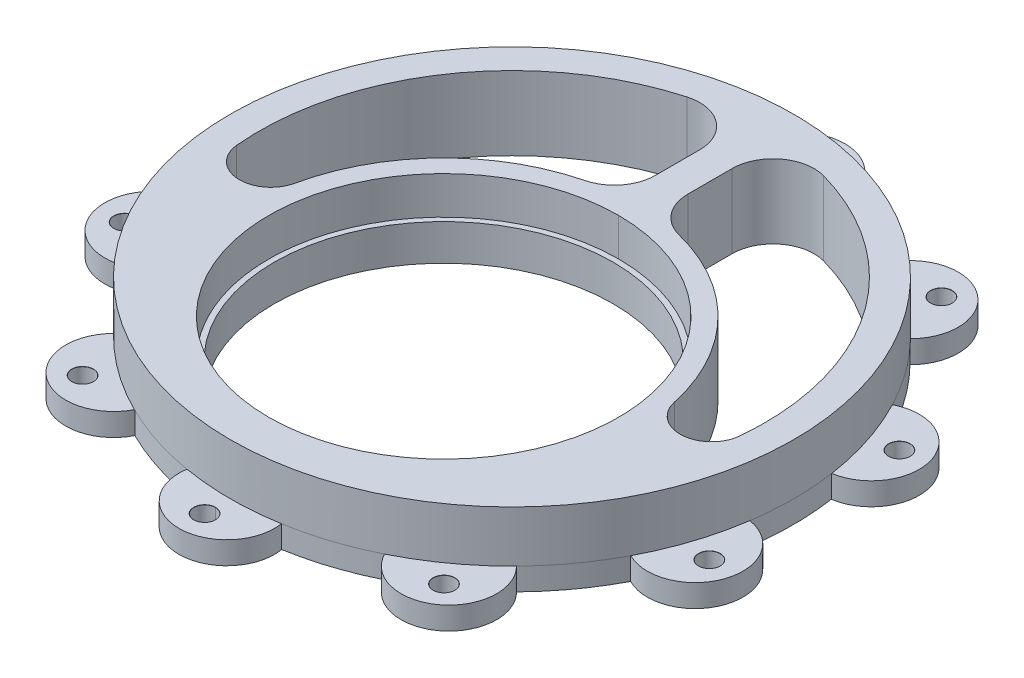
SolidWorks part; units mm, degrees
material "6061-T6 (SS)"
ref_plane "X-Y Datum" through (0, 0, 0) normal (0, 0, 1) x (1, 0, 0)
ref_plane "X-Z Datum" through (0, 0, 0) normal (0, 1, 0) x (1, 0, 0)
ref_plane "Y-Z Datum" through (0, 0, 0) normal (1, 0, 0) x (0, 0, -1)
sketch "Sketch1" plane through (0, 0, 0) normal (0, 1, 0) x (1, 0, 0)
  line L0 (0, 0) -> (0, -12.7) construction
  line L1 (0, -43.0151) -> (0, 43.0151) construction
  line L2 (0, 52.3875) -> (0, 61.9125) construction
  circle A0 centre (0, -12.7) radius 30.988
  circle A1 centre (0, 0) radius 52.3875 construction
  circle A2 centre (0, 0) radius 61.9125
  circle A3 centre (0, 0) radius 57.15 construction
  point P12 (0, 57.15)
  dimension "D2" = 61.976
  dimension "D3" = 104.775
  dimension "D4" = 123.825
  dimension "D5" = 114.3
  dimension "D1" = 12.7
extrude "Slotted-Body Extrude" add sketch "Sketch1" along normal blind 4.191
sketch "Sketch5" plane through (0, 4.191, 0) normal (0, 1, 0) x (1, 0, 0)
  circle A0 centre (0, 0) radius 52.3875 construction
  circle A1 centre (0, 0) radius 52.3875
extrude "Boss-Extrude3" add sketch "Sketch5" along normal blind 9.525
sketch "Sketch6" plane through (0, 0, 0) normal (0, -1, 0) x (1, 0, 0)
  line L0 (0, -79.2756) -> (0, 0) construction
  line L2 (3.014, -37.9067) -> (3.014, -29.6741)
  line L4 (-3.014, -37.9067) -> (-3.014, -29.6741)
  circle A0 centre (0, 12.7) radius 30.988 construction
  circle A1 centre (0, 12.7) radius 30.988 construction
  circle A2 centre (0, 12.7) radius 32.512
  arc A9 (-35.2562, 5.0907) -> (-8.7792, -22.2832) centre (0, 12.7) ccw
  arc A10 (-46.783, 4.406) -> (-12.6921, -45.2435) centre (0, 0) ccw
  arc A11 (-46.783, 4.406) -> (-35.2562, 5.0907) centre (-40.9667, 3.8583) cw
  arc A19 (-3.014, -29.6741) -> (-8.7792, -22.2832) centre (-10.634, -29.6741) ccw
  arc A20 (-3.014, -37.9067) -> (-12.6921, -45.2435) centre (-10.634, -37.9067) cw
  circle A21 centre (0, 0) radius 61.9125 construction
  arc A27 (46.783, 4.406) -> (35.2562, 5.0907) centre (40.9667, 3.8583) ccw
  arc A28 (46.783, 4.406) -> (12.6921, -45.2435) centre (0, 0) cw
  arc A29 (3.014, -37.9067) -> (12.6921, -45.2435) centre (10.634, -37.9067) ccw
  arc A30 (3.014, -29.6741) -> (8.7792, -22.2832) centre (10.634, -29.6741) cw
  arc A31 (35.2562, 5.0907) -> (8.7792, -22.2832) centre (0, 12.7) cw
  point P30 (0, 0)
  point P31 (-3.014, -23.2419)
  point P32 (0, 0)
  point P36 (-3.014, -46.8932)
  dimension "D1" = 65.024
  dimension "D2" = 7.62
  dimension "D3" = 5.842
  dimension "D4" = 46.99
  dimension "D5" = 7.62
  dimension "D6" = 36.068
  dimension "D8" = 8.2326
extrude "Cut-Extrude5" cut sketch "Sketch6" against normal through all
sketch "Sketch8" plane through (0, 0, 0) normal (0, -1, 0) x (1, 0, 0)
  circle A0 centre (0, 12.7) radius 32.512 construction
  circle A1 centre (0, 12.7) radius 32.512
  circle A2 centre (0, 12.7) radius 31.496
  dimension "D1" = 62.992
extrude "Boss-Extrude4" add sketch "Sketch8" against normal blind 6.7 separate body
hole_wizard "Ø4.0mm Dowel Hole2" positions "Sketch9" profile "Sketch10" hole size "Ø4.0" standard "ANSI Metric" end condition through all
sketch "Sketch9" plane through (0, 4.191, 0) normal (0, 1, 0) x (1, 0, 0)
  point P0 (0, 57.15)
sketch "Sketch10" plane through (0, 4.191, -57.15) normal (1, 0, 0) x (0, 0, 1)
  line L0 (0, 0) -> (0, 4.191)
  line L1 (0, 4.191) -> (2, 4.191)
  line L2 (2, 4.191) -> (2, 0.025)
  line L3 (2, 0.025) -> (2.025, 0)
  line L5 (2.025, 0) -> (0, 0)
  line L6 (-2, 0.025) -> (-2.025, 0) construction
  line L11 (0, -6.35) -> (0, 107.95) construction
  dimension "Thru Hole Dia." = 4
  dimension "Thru Hole Depth" = 4.191
  dimension "Near C'Sink Dia." = 4.05
  dimension "Near C'Sink Angle" = 90
pattern_circular "CirPattern1" count 10 over 360 about axis through (0, 13.716, 0) along (0, -1, 0) of "Ø4.0mm Dowel Hole2"
ref_point "Point1"
ref_plane "Plane1" through (0, 0, 0) normal (1, 0, 0) x (0, 0, -1)
split line "Split Line1"
ref_point "Point4"
ref_point "Point5"
split line "Split Line2"
split line "Split Line3"
sketch "Sketch14" plane through (0, 4.191, 0) normal (0, 1, 0) x (1, 0, 0)
  arc A2 (-8.7727, 51.5833) -> (8.7727, 51.5833) centre (0, 53.0225) cw
  circle A3 centre (0, 0) radius 61.9125 construction
  circle A4 centre (0, 0) radius 52.324 construction
  arc A5 (-8.7727, 51.5833) -> (8.7727, 51.5833) centre (0, 0) cw
  arc A6 (23.2226, 46.8883) -> (37.4172, 36.5753) centre (0, 0) cw
  arc A7 (23.2226, 46.8883) -> (37.4172, 36.5753) centre (31.1658, 42.8961) cw
  arc A8 (46.3477, 24.2835) -> (51.7696, 7.5968) centre (0, 0) cw
  arc A9 (46.3477, 24.2835) -> (51.7696, 7.5968) centre (50.4274, 16.3849) cw
  arc A10 (51.7696, -7.5968) -> (46.3477, -24.2835) centre (0, 0) cw
  arc A11 (51.7696, -7.5968) -> (46.3477, -24.2835) centre (50.4274, -16.3849) cw
  arc A12 (37.4172, -36.5753) -> (23.2226, -46.8883) centre (0, 0) cw
  arc A13 (37.4172, -36.5753) -> (23.2226, -46.8883) centre (31.1658, -42.8961) cw
  arc A14 (8.7727, -51.5833) -> (-8.7727, -51.5833) centre (0, 0) cw
  arc A15 (8.7727, -51.5833) -> (-8.7727, -51.5833) centre (0, -53.0225) cw
  arc A16 (-23.2226, -46.8883) -> (-37.4172, -36.5753) centre (0, 0) cw
  arc A17 (-23.2226, -46.8883) -> (-37.4172, -36.5753) centre (-31.1658, -42.8961) cw
  arc A18 (-46.3477, -24.2835) -> (-51.7696, -7.5968) centre (0, 0) cw
  arc A19 (-46.3477, -24.2835) -> (-51.7696, -7.5968) centre (-50.4274, -16.3849) cw
  arc A20 (-51.7696, 7.5968) -> (-46.3477, 24.2835) centre (0, 0) cw
  arc A21 (-51.7696, 7.5968) -> (-46.3477, 24.2835) centre (-50.4274, 16.3849) cw
  arc A22 (-37.4172, 36.5753) -> (-23.2226, 46.8883) centre (0, 0) cw
  arc A23 (-37.4172, 36.5753) -> (-23.2226, 46.8883) centre (-31.1658, 42.8961) cw
  point P9 (0, 57.15)
  point P10 (0, 61.9125)
  point P41 (0, 0)
  dimension "D1" = 104.648
  dimension "D2" = 8.89
  dimension "D3" = 10
sketch "Sketch15" plane through (0, 4.191, 0) normal (0, 1, 0) x (1, 0, 0)
  arc A0 (-23.2226, 46.8883) -> (-36.3913, 50.0883) centre (-31.1658, 42.8961) ccw
  arc A1 (-23.2226, 46.8883) -> (-37.4172, 36.5753) centre (-31.1658, 42.8961) ccw construction
  arc A2 (-8.7727, 51.5833) -> (-23.2226, 46.8883) centre (0, 0) ccw
  arc A3 (-8.7727, 51.5833) -> (0, 61.9125) centre (0, 53.0225) cw
  arc A4 (8.7727, 51.5833) -> (-8.7727, 51.5833) centre (0, 53.0225) ccw construction
  arc A5 (0, 61.9125) -> (-36.3913, 50.0883) centre (0, 0) ccw
  dimension "D1" = 61.9125
  dimension "D2" = 52.324
extrude "Cut-Extrude9" cut sketch "Sketch15" against normal through all
pattern_circular "CirPattern6" count 10 over 360 about axis through (0, 4.191, 0) along (0, 1, 0) of "Cut-Extrude9"
